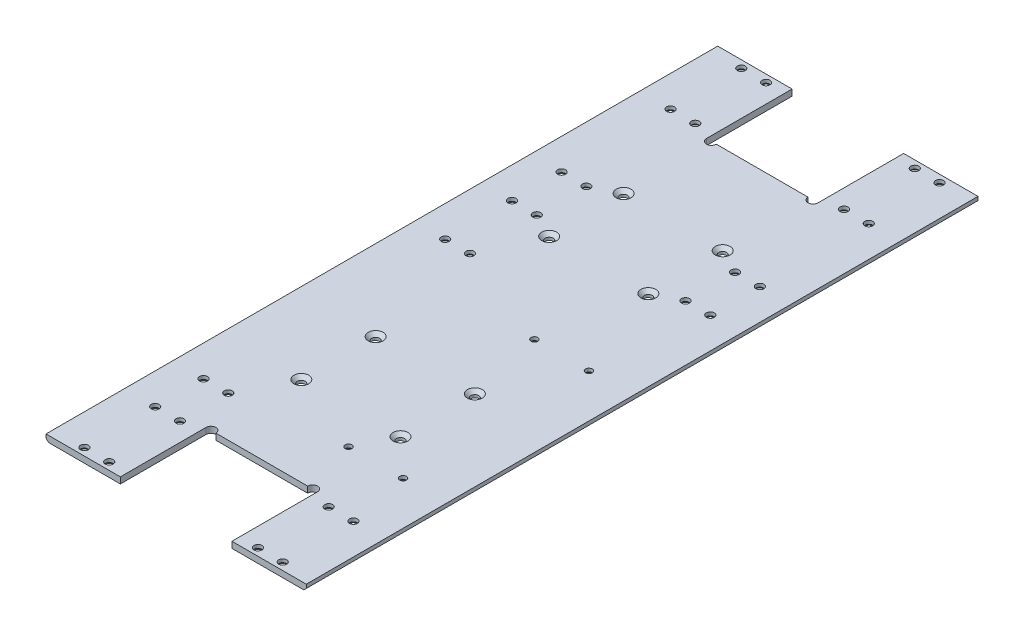
SolidWorks part; units mm, degrees
ref_plane "前视基准面" through (0, 0, 0) normal (0, 0, 1) x (1, 0, 0)
ref_plane "上视基准面" through (0, 0, 0) normal (0, 1, 0) x (1, 0, 0)
ref_plane "右视基准面" through (0, 0, 0) normal (1, 0, 0) x (0, 0, -1)
sketch "草图1" plane through (0, 0, 0) normal (0, 1, 0) x (1, 0, 0)
  line L6 (-52.5, -135.5) -> (52.5, -135.5)
  line L7 (52.5, -135.5) -> (52.5, 135.5)
  line L8 (-52.5, 135.5) -> (52.5, 135.5)
  line L9 (-52.5, -135.5) -> (-52.5, 135.5)
  point P8 (-50, 0)
extrude "凸台-拉伸1" add sketch "草图1" along normal blind 2.5
sketch "草图2" plane through (0, 2.5, 0) normal (0, 1, 0) x (1, 0, 0)
  circle A14 centre (35, -3.95) radius 1.35
  circle A15 centre (13, -3.95) radius 1.35
  circle A18 centre (35, -78.95) radius 1.35
  circle A19 centre (13, -78.95) radius 1.35
  circle A32 centre (20, -35) radius 1.6
  circle A33 centre (-20, -35) radius 1.6
  circle A34 centre (20, -65) radius 1.6
  circle A35 centre (-20, -65) radius 1.6
  circle A36 centre (-20, 35) radius 1.6
  circle A37 centre (20, 35) radius 1.6
  circle A40 centre (-20, 65) radius 1.6
  circle A41 centre (20, 65) radius 1.6
extrude "切除-拉伸1" cut sketch "草图2" against normal blind 10
sketch "草图7" plane through (0, 2.5, 0) normal (0, 1, 0) x (1, 0, 0)
  line L0 (0, -1.375) -> (0, 1.375) construction
  circle A0 centre (-40, 60) radius 1.6
  circle A1 centre (-30, 60) radius 1.6
  circle A2 centre (30, 60) radius 1.6
  circle A3 centre (40, 60) radius 1.6
  circle A4 centre (-40, 40) radius 1.6
  circle A5 centre (-30, 40) radius 1.6
  circle A6 centre (30, 40) radius 1.6
  circle A7 centre (40, 40) radius 1.6
  dimension "D1" = 2
chamfer "倒角4" distance 1.4 angle 45 8 edges at (-20, 2.5, 63.4) (-20, 2.5, 33.4) (20, 2.5, 66.6) (20, 2.5, 36.6) (-20, 2.5, -33.4) (-20, 2.5, -63.4) (20, 2.5, -36.6) (20, 2.5, -66.6)
chamfer "倒角5" distance 1 angle 45 2 edges at (52.5, 0, 0) (-52.5, 0, 0)
sketch "草图4" plane through (0, 0, 0) normal (0, -1, 0) x (1, 0, 0)
  line L0 (1.375, 0) -> (-1.375, 0) construction
  line L1 (-51.5, 135.5) -> (51.5, 135.5) construction
  line L2 (0, 100.95) -> (22.5, 100.95)
  line L3 (22.5, 100.95) -> (22.5, 135.5)
  line L4 (22.5, 135.5) -> (-22.5, 135.5)
  line L5 (-22.5, 135.5) -> (-22.5, 100.95)
  line L6 (-22.5, 100.95) -> (0, 100.95)
  line L7 (-22.5, -100.95) -> (0, -100.95)
  line L8 (-22.5, -135.5) -> (-22.5, -100.95)
  line L9 (22.5, -135.5) -> (-22.5, -135.5)
  line L10 (22.5, -100.95) -> (22.5, -135.5)
  line L11 (0, -100.95) -> (22.5, -100.95)
extrude "切除-拉伸2" cut sketch "草图4" against normal blind 10
sketch "草图6" plane through (0, 0, 0) normal (0, -1, 0) x (1, 0, 0)
  line L0 (0, -1.375) -> (0, 1.375) construction
  line L2 (1.375, 0) -> (-1.375, 0) construction
  circle A0 centre (-40, 132.5) radius 1.6
  circle A1 centre (-30, 132.5) radius 1.6
  circle A2 centre (-30, 103.95) radius 1.6
  circle A3 centre (-40, 103.95) radius 1.6
  circle A4 centre (40, 103.95) radius 1.6
  circle A5 centre (30, 103.95) radius 1.6
  circle A6 centre (30, 132.5) radius 1.6
  circle A7 centre (40, 132.5) radius 1.6
  circle A8 centre (40, -132.5) radius 1.6
  circle A9 centre (30, -132.5) radius 1.6
  circle A10 centre (30, -103.95) radius 1.6
  circle A11 centre (40, -103.95) radius 1.6
  circle A12 centre (-40, -103.95) radius 1.6
  circle A13 centre (-30, -103.95) radius 1.6
  circle A14 centre (-30, -132.5) radius 1.6
  circle A15 centre (-40, -132.5) radius 1.6
extrude "切除-拉伸3" cut sketch "草图6" against normal blind 10
extrude "切除-拉伸4" cut sketch "草图7" against normal blind 10
sketch "草图8" plane through (0, 0, 0) normal (0, -1, 0) x (1, 0, 0)
  line L4 (-40, 132.5) -> (-30, 132.5)
  circle A1 centre (-40, 84.45) radius 1.6
  circle A2 centre (-30, 84.45) radius 1.6
  circle A3 centre (-40, -13.05) radius 1.6
  circle A4 centre (-30, -13.05) radius 1.6
extrude "切除-拉伸5" cut sketch "草图8" against normal blind 10 contours A1 | A2 | A4 | A3 region at (-40, 0, 84.45)
sketch "草图9" plane through (0, 0, 0) normal (0, -1, 0) x (1, 0, 0)
  line L0 (0, -1.375) -> (0, 1.375) construction
  line L1 (1.375, 0) -> (-1.375, 0) construction
  line L2 (-22.5, 100.95) -> (22.5, 100.95) construction
  circle A3 centre (20.5, 100.95) radius 2
  circle A4 centre (-20.5, 100.95) radius 2
  circle A5 centre (-20.5, -100.95) radius 2
  circle A6 centre (20.5, -100.95) radius 2
extrude "切除-拉伸6" cut sketch "草图9" against normal blind 10
chamfer "倒角3" distance 1.15 angle 45 32 edges at (13, 0, 2.6) (35, 0, 2.6) (35, 0, 77.6) (13, 0, 77.6) (40, 0, 102.35) (40, 0, 134.1) (30, 0, 102.35) (30, 0, 134.1) (-30, 0, 105.55) (-30, 0, 130.9) (-40, 0, 105.55) (-40, 0, 130.9) (40, 0, -102.35) (40, 0, -134.1) (30, 0, -134.1) (30, 0, -102.35) (-30, 0, -130.9) (-30, 0, -105.55) (-40, 0, -130.9) (-40, 0, -105.55) (40, 0, -61.6) (30, 0, -61.6) (-30, 0, -61.6) (-40, 0, -61.6) (-30, 0, -14.65) (-40, 0, -14.65) (-30, 0, 82.85) (-40, 0, 82.85) (-40, 0, -41.6) (-30, 0, -41.6) (30, 0, -41.6) (40, 0, -41.6)
